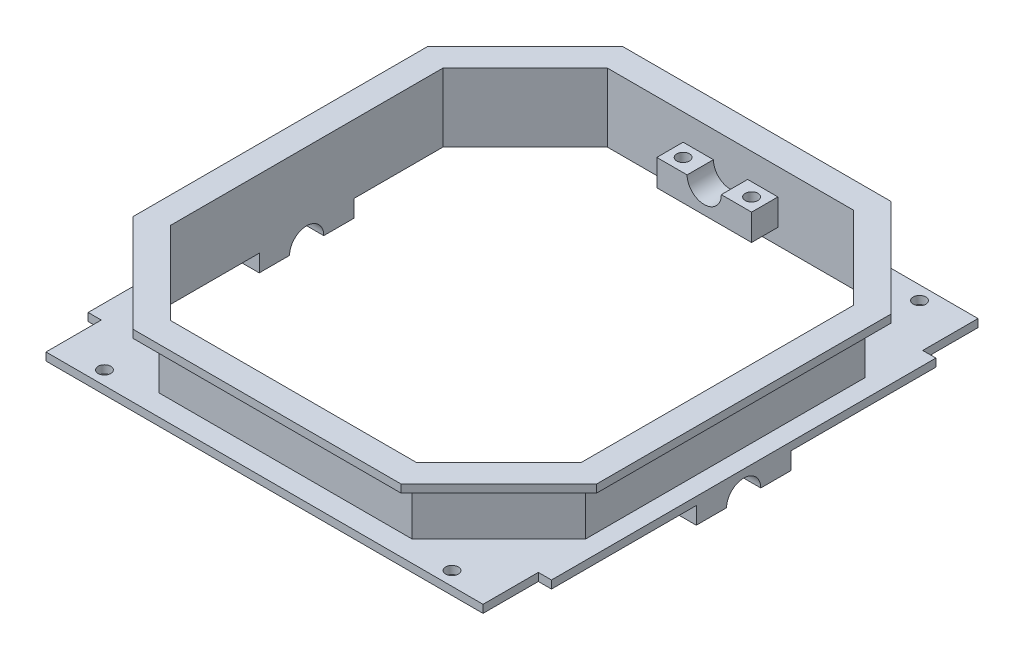
SolidWorks part; units mm, degrees
ref_plane "Front Plane" through (0, 0, 0) normal (0, 0, 1) x (1, 0, 0)
ref_plane "Top Plane" through (0, 0, 0) normal (0, 1, 0) x (1, 0, 0)
ref_plane "Right Plane" through (0, 0, 0) normal (1, 0, 0) x (0, 0, -1)
sketch "Sketch1" plane through (0, 0, 0) normal (0, 1, 0) x (1, 0, 0)
  line L5 (-44, -46.5) -> (44, -46.5)
  line L6 (-44, -46.5) -> (-44, 46.5)
  line L7 (-44, 46.5) -> (44, 46.5)
  line L8 (44, -46.5) -> (44, 46.5)
  line L9 (-44, -46.5) -> (44, 46.5) construction
  line L10 (-44, 46.5) -> (44, -46.5) construction
  point P0 (0, 0)
  dimension "D1" = 88
  dimension "D2" = 93
extrude "Boss-Extrude1" add sketch "Sketch1" along normal blind 13
sketch "Sketch2" plane through (0, 13, 0) normal (0, 1, 0) x (1, 0, 0)
  line L0 (0, 46.5) -> (0, -46.5) construction
  line L1 (-44, -46.5) -> (44, -46.5) construction
  line L2 (-44, 0) -> (44, 0) construction
  line L3 (44, -46.5) -> (44, 46.5) construction
  line L4 (-24, -43) -> (-40.5, -26.5)
  line L5 (-44, 46.5) -> (-44, -46.5) construction
  line L6 (-44, -36.5) -> (-44, -46.5)
  line L7 (-44, -46.5) -> (-34, -46.5)
  line L11 (-24, -43) -> (24, -43)
  line L14 (-34, -46.5) -> (34, -46.5)
  line L15 (-40.5, -26.5) -> (-40.5, 26.5)
  line L17 (-44, -36.5) -> (-44, 36.5)
  line L18 (44, -36.5) -> (44, 36.5)
  line L19 (40.5, -26.5) -> (40.5, 26.5)
  line L20 (44, -46.5) -> (34, -46.5)
  line L21 (44, -36.5) -> (44, -46.5)
  line L22 (24, -43) -> (40.5, -26.5)
  line L23 (24, 43) -> (40.5, 26.5)
  line L24 (44, 36.5) -> (44, 46.5)
  line L25 (44, 46.5) -> (34, 46.5)
  line L26 (-34, 46.5) -> (34, 46.5)
  line L27 (-24, 43) -> (24, 43)
  line L28 (-44, 46.5) -> (-34, 46.5)
  line L29 (-44, 36.5) -> (-44, 46.5)
  line L30 (-24, 43) -> (-40.5, 26.5)
  point P6 (0, 0)
  point P12 (0, 0)
  point P29 (0, -43)
  point P35 (40.5, 0)
  point P37 (-40.5, 0)
  point P40 (0, 43)
  dimension "D1" = 45
  dimension "D2" = 10
  dimension "D3" = 10
  dimension "D4" = 3.5
  dimension "D5" = 3.5
  dimension "D6" = 20
extrude "Cut-Extrude1" cut sketch "Sketch2" against normal offset from surface (11.5 mm away) 1.5 up to face at (0, 0, 0)
sketch "Sketch3" plane through (0, 13, 0) normal (0, 1, 0) x (1, 0, 0)
  line L16 (-23.3787, -41.5) -> (23.3787, -41.5)
  line L17 (23.3787, -41.5) -> (39, -25.8787)
  line L18 (39, -25.8787) -> (39, 25.8787)
  line L19 (39, 25.8787) -> (23.3787, 41.5)
  line L20 (23.3787, 41.5) -> (-23.3787, 41.5)
  line L21 (-23.3787, 41.5) -> (-39, 25.8787)
  line L22 (-39, 25.8787) -> (-39, -25.8787)
  line L23 (-39, -25.8787) -> (-23.3787, -41.5)
  line L24 (-23.3787, -41.5) -> (23.3787, -41.5)
  line L25 (23.3787, -41.5) -> (39, -25.8787)
  line L26 (39, -25.8787) -> (39, 25.8787)
  line L27 (39, 25.8787) -> (23.3787, 41.5)
  line L28 (23.3787, 41.5) -> (-23.3787, 41.5)
  line L29 (-23.3787, 41.5) -> (-39, 25.8787)
  line L30 (-39, 25.8787) -> (-39, -25.8787)
  line L31 (-39, -25.8787) -> (-23.3787, -41.5)
  dimension "D1" = 1.5
extrude "Cut-Extrude2" cut sketch "Sketch3" against normal through all
sketch "Sketch4" plane through (0, 0, -41.5) normal (0, 0, 1) x (1, 0, 0)
  line L0 (0, 0) -> (0, 8) construction
  line L1 (23.3787, 0) -> (-23.3787, 0) construction
  line L2 (3.25, 8) -> (9, 8)
  line L5 (3.25, 8) -> (-3.25, 8) construction
  line L8 (-9, 3) -> (9, 3)
  line L9 (9, 3) -> (9, 8)
  line L10 (23.3787, 13) -> (-23.3787, 13) construction
  line L11 (-9, 3) -> (-9, 8)
  line L12 (-3.25, 8) -> (-9, 8)
  arc A0 (-3.25, 8) -> (3.25, 8) centre (0, 8) ccw
  point P13 (0, 3)
  dimension "D1" = 3.25
  dimension "D2" = 18
  dimension "D3" = 5
  dimension "D4" = 5
extrude "Boss-Extrude2" add sketch "Sketch4" along normal blind 5
sketch "Sketch5" plane through (39, 0, 0) normal (-1, 0, 0) x (0, 0, 1)
  line L0 (0, 0) -> (0, -3.25) construction
  line L2 (25.8787, 0) -> (-25.8787, 0) construction
  line L3 (3.25, -3.25) -> (9, -3.25)
  line L4 (9, -3.25) -> (9, 0)
  line L6 (-9, -3.25) -> (-9, 0)
  line L7 (-3.25, -3.25) -> (-9, -3.25)
  line L8 (-9, 0) -> (9, 0)
  arc A1 (3.25, -3.25) -> (-3.25, -3.25) centre (0, -3.25) ccw
  line M14 (-25.8787, 0) -> (25.8787, 0)
  dimension "D2" = 3.25
  dimension "D1" = 6.5
  dimension "D3" = 18
extrude "Boss-Extrude5" add sketch "Sketch4<2>" against normal blind 5 from surface starting at face at (0, 6.5, 41.5)
sketch "Sketch4<2>" plane through (0, 0, -41.5) normal (0, 0, 1) x (1, 0, 0) same geometry as "Sketch4"
sketch "Sketch6" plane through (0, 1.5, 0) normal (0, 1, 0) x (1, 0, 0)
  line L0 (-44, 0) -> (44, 0) construction
  line L1 (44, -46.5) -> (41.5, -46.5)
  line L2 (44, -46.5) -> (44, -36.5)
  line L3 (44, -36.5) -> (41.5, -36.5)
  line L4 (41.5, -46.5) -> (41.5, -36.5)
  line L5 (44, -46.5) -> (44, 46.5) construction
  line L6 (0, -46.5) -> (0, 46.5) construction
  line L7 (44, 46.5) -> (-44, 46.5) construction
  line L8 (41.5, 46.5) -> (41.5, 36.5)
  line L9 (44, 36.5) -> (41.5, 36.5)
  line L10 (44, 46.5) -> (44, 36.5)
  line L11 (44, 46.5) -> (41.5, 46.5)
  line L12 (-44, 46.5) -> (-41.5, 46.5)
  line L13 (-44, 46.5) -> (-44, 36.5)
  line L14 (-44, 36.5) -> (-41.5, 36.5)
  line L15 (-41.5, 46.5) -> (-41.5, 36.5)
  line L16 (-41.5, -46.5) -> (-41.5, -36.5)
  line L17 (-44, -36.5) -> (-41.5, -36.5)
  line L18 (-44, -46.5) -> (-44, -36.5)
  line L19 (-44, -46.5) -> (-41.5, -46.5)
  point P12 (0, 0)
  point P17 (0, 0)
  dimension "D1" = 2.5
  dimension "D2" = 10
extrude "Cut-Extrude3" cut sketch "Sketch6" against normal through all
sketch "Sketch8" plane through (0, 0, -46.5) normal (0, 0, -1) x (-1, 0, 0)
  line L4 (-41.5, 0) -> (41.5, 0)
  line L5 (41.5, 0) -> (41.5, 1.5)
  line L6 (41.5, 1.5) -> (-41.5, 1.5)
  line L7 (-41.5, 1.5) -> (-41.5, 0)
  line L8 (-41.5, 0) -> (41.5, 0)
  line L9 (41.5, 0) -> (41.5, 1.5)
  line L10 (41.5, 1.5) -> (-41.5, 1.5)
  line L11 (-41.5, 1.5) -> (-41.5, 0)
  dimension "D1" = 0
extrude "Boss-Extrude6" add sketch "Sketch8" along normal blind 0.5
mirror "Mirror1" about plane through (0, 0, 0) normal (0, 0, 1) of "Boss-Extrude6"
sketch "Sketch9" plane through (0, 0, 0) normal (0, 1, 0) x (1, 0, 0)
  line L0 (41.5, -36.5) -> (41.5, -47) construction
  line L1 (-41.5, -47) -> (41.5, -47) construction
  line L2 (-44, 0) -> (44, 0) construction
  line L3 (44, -36.5) -> (44, 36.5) construction
  line L4 (0, -47) -> (0, 47) construction
  line L5 (-41.5, 47) -> (41.5, 47) construction
  circle A0 centre (33, -44.4) radius 1.2
  circle A1 centre (33, 44.4) radius 1.2
  circle A2 centre (-33, 44.4) radius 1.2
  circle A3 centre (-33, -44.4) radius 1.2
  point P12 (0, 0)
  point P18 (0, 0)
  dimension "D1" = 8.5
  dimension "D2" = 2.6
  dimension "D3" = 2.4
extrude "Cut-Extrude4" cut sketch "Sketch9" along normal through all
extrude "Boss-Extrude7" add sketch "Sketch5" against normal up to surface (5 mm away) contours A1 L6 L7 M14 | A1 L3 L4 L8 region at (39, -1.5277, 5.7355) region at (39, -1.5277, -5.7355) up to face at (44, 0.75, 0)
extrude "Boss-Extrude8" add sketch "Sketch5<4>" along normal up to surface (83 mm away) from surface contours A1 L6 L7 M14 | A1 L3 L4 L8 region at (39, -1.5277, 5.7355) region at (39, -1.5277, -5.7355) up to face at (-44, 0.75, 0) starting at face at (-39, 6.5, 0)
sketch "Sketch5<4>" plane through (39, 0, 0) normal (-1, 0, 0) x (0, 0, 1) same geometry as "Sketch5"
sketch "Sketch10" plane through (0, 0, 0) normal (0, 1, 0) x (1, 0, 0)
  circle A0 centre (-6.5, -39) radius 1.2 construction
  circle A1 centre (6.5, -39) radius 1.2 construction
  circle A2 centre (6.5, 39) radius 1.2 construction
  circle A3 centre (-6.5, 39) radius 1.2 construction
  circle A4 centre (-6.5, -39) radius 1.2
  circle A5 centre (6.5, -39) radius 1.2
  circle A6 centre (6.5, 39) radius 1.2
  circle A7 centre (-6.5, 39) radius 1.2
extrude "Cut-Extrude5" cut sketch "Sketch10" along normal through all
sketch "Sketch11" plane through (0, 0, 0) normal (0, 1, 0) x (1, 0, 0)
  circle A0 centre (41.5, -6.5) radius 1.2 construction
  circle A1 centre (41.5, 6.5) radius 1.2 construction
  circle A2 centre (-41.5, -6.5) radius 1.2 construction
  circle A3 centre (-41.5, 6.5) radius 1.2 construction
  circle A4 centre (41.5, -6.5) radius 1.2
  circle A5 centre (41.5, 6.5) radius 1.2
  circle A6 centre (-41.5, -6.5) radius 1.2
  circle A7 centre (-41.5, 6.5) radius 1.2
extrude "Cut-Extrude6" cut sketch "Sketch11" against normal through all
sketch "Sketch12" plane through (0, 13, 0) normal (0, 1, 0) x (1, 0, 0)
  line L16 (-25.4497, -46.5) -> (25.4497, -46.5)
  line L17 (25.4497, -46.5) -> (44, -27.9497)
  line L18 (44, -27.9497) -> (44, 27.9497)
  line L19 (44, 27.9497) -> (25.4497, 46.5)
  line L20 (25.4497, 46.5) -> (-25.4497, 46.5)
  line L21 (-25.4497, 46.5) -> (-44, 27.9497)
  line L22 (-44, 27.9497) -> (-44, -27.9497)
  line L23 (-44, -27.9497) -> (-25.4497, -46.5)
  line L24 (-25.4497, -46.5) -> (25.4497, -46.5)
  line L25 (25.4497, -46.5) -> (44, -27.9497)
  line L26 (44, -27.9497) -> (44, 27.9497)
  line L27 (44, 27.9497) -> (25.4497, 46.5)
  line L28 (25.4497, 46.5) -> (-25.4497, 46.5)
  line L29 (-25.4497, 46.5) -> (-44, 27.9497)
  line L30 (-44, 27.9497) -> (-44, -27.9497)
  line L31 (-44, -27.9497) -> (-25.4497, -46.5)
  line L40 (40.5, 26.5) -> (24, 43) construction
  line L41 (40.5, -26.5) -> (40.5, 26.5) construction
  line L42 (24, -43) -> (40.5, -26.5) construction
  line L43 (-24, -43) -> (24, -43) construction
  line L44 (-40.5, -26.5) -> (-24, -43) construction
  line L45 (-40.5, 26.5) -> (-40.5, -26.5) construction
  line L46 (24, 43) -> (-24, 43) construction
  line L47 (-24, 43) -> (-40.5, 26.5) construction
  line L48 (40.5, 26.5) -> (24, 43)
  line L49 (40.5, -26.5) -> (40.5, 26.5)
  line L50 (24, -43) -> (40.5, -26.5)
  line L51 (-24, -43) -> (24, -43)
  line L52 (-40.5, -26.5) -> (-24, -43)
  line L53 (-40.5, 26.5) -> (-40.5, -26.5)
  line L54 (24, 43) -> (-24, 43)
  line L55 (-24, 43) -> (-40.5, 26.5)
  dimension "D1" = 3.5
extrude "Boss-Extrude9" add sketch "Sketch12" against normal blind 1.5
